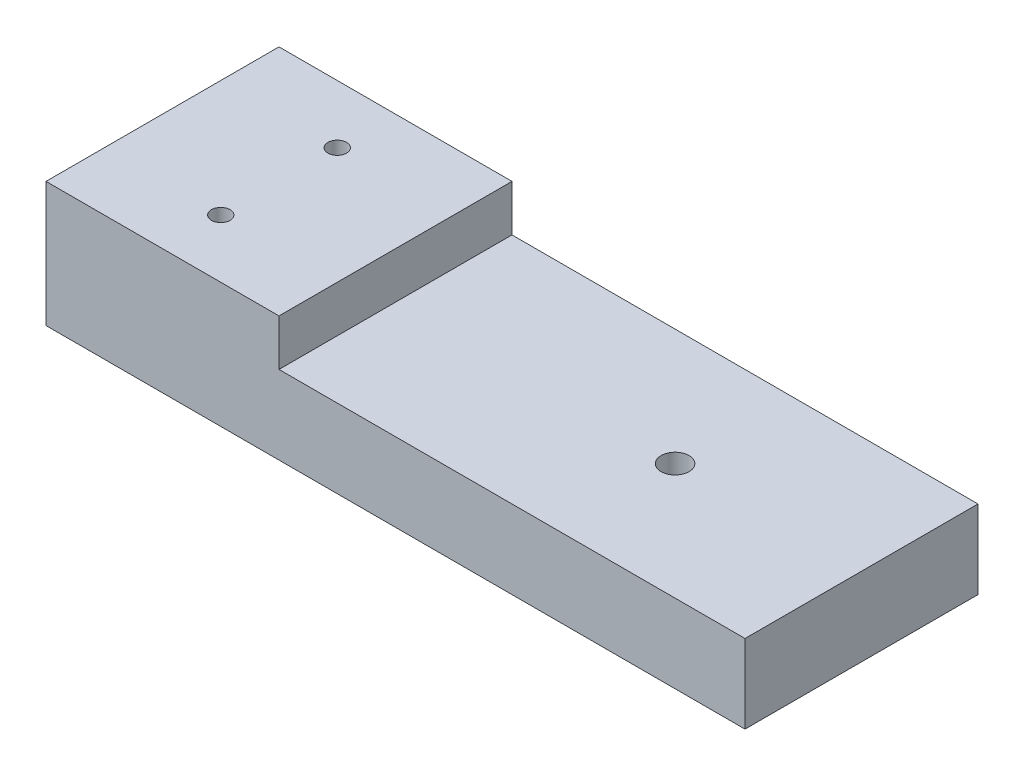
SolidWorks part; units mm, degrees
material "Balsa"
ref_plane "Front Plane" through (0, 0, 0) normal (0, 0, 1) x (1, 0, 0)
ref_plane "Top Plane" through (0, 0, 0) normal (0, 1, 0) x (1, 0, 0)
ref_plane "Right Plane" through (0, 0, 0) normal (1, 0, 0) x (0, 0, -1)
sketch "Sketch1" plane through (0, 0, 0) normal (0, 1, 0) x (1, 0, 0)
  line L1 (0, 0) -> (50, 0)
  line L2 (0, 0) -> (0, 50)
  line L3 (0, 50) -> (50, 50)
  line L4 (50, 0) -> (50, 50)
  line L5 (0, 0) -> (50, 50) construction
  line L6 (0, 50) -> (50, 0) construction
  line L7 (0, 50) -> (150, 50)
  line L8 (0, 50) -> (0, 0)
  line L9 (0, 0) -> (150, 0)
  line L10 (150, 50) -> (150, 0)
  line L11 (0, 50) -> (150, 0) construction
  line L12 (0, 0) -> (150, 50) construction
  point P4 (25, 25)
  point P8 (75, 25)
  dimension "D1" = 50
  dimension "D3" = 100
  dimension "D4" = 50
extrude "Boss-Extrude1" add sketch "Sketch1" along normal blind 26.8 contours L1 L4 L3 L2 region at (25, 0, -25)
extrude "Boss-Extrude2" add sketch "Sketch1<3>" along normal blind 16.85 contours L10 L7 L4 L9 region at (100, 0, -25)
sketch "Sketch1<3>" plane through (0, 0, 0) normal (0, 1, 0) x (1, 0, 0) same geometry as "Sketch1"
sketch "Sketch2" plane through (0, 0, 0) normal (0, -1, 0) x (1, 0, 0)
  line L0 (0, 0) -> (50, 0) construction
  line L1 (0, 0) -> (150, 0) construction
  line L2 (25, 0) -> (25, -50)
  line L3 (0, -50) -> (150, -50) construction
  line L4 (25, -25) -> (150, -25)
  line L5 (150, -50) -> (150, 0) construction
  circle A0 centre (25, -37.5) radius 2
  circle A1 centre (25, -12.5) radius 2
  circle A2 centre (110, -25) radius 3
  point P5 (25, 0)
  dimension "D2" = 25
  dimension "D3" = 12.5
  dimension "D4" = 4
  dimension "D5" = 4
  dimension "D6" = 6
  dimension "D7" = 40
  dimension "D1" = 50
  dimension "D8" = 25
extrude "Cut-Extrude1" cut sketch "Sketch2" against normal through all contours A1 | A0 | A2
